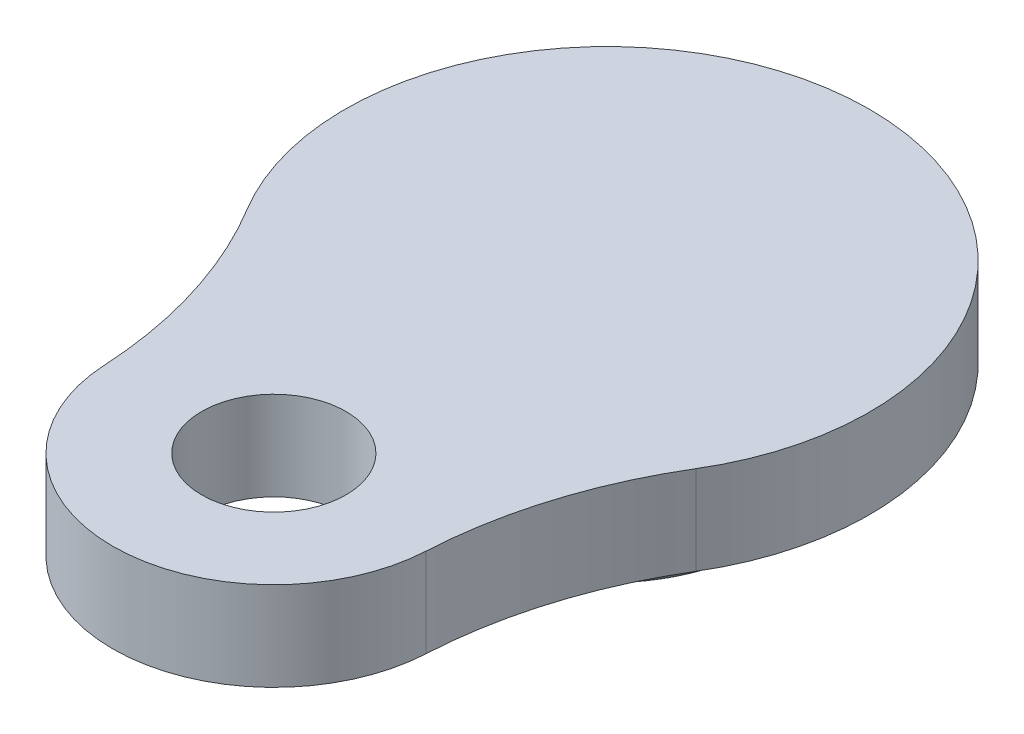
SolidWorks part; units mm, degrees
ref_plane "Front Plane" through (0, 0, 0) normal (0, 0, 1) x (1, 0, 0)
ref_plane "Top Plane" through (0, 0, 0) normal (0, 1, 0) x (1, 0, 0)
ref_plane "Right Plane" through (0, 0, 0) normal (1, 0, 0) x (0, 0, -1)
sketch "Sketch1" plane through (0, 0, 0) normal (0, 1, 0) x (1, 0, 0)
  line L0 (0, -7.5) -> (0, 0) construction
  circle A0 centre (0, 0) radius 3.9
  circle A3 centre (0, -7.5) radius 1.625
  arc A4 (-3.6198, -7.6937) -> (3.6198, -7.6937) centre (0, -7.5) ccw
  arc A5 (-5.0486, -3.0531) -> (-3.6198, -7.6937) centre (-13.6055, -8.228) cw
  arc A6 (5.0486, -3.0531) -> (-5.0486, -3.0531) centre (0, 0) ccw
  arc A7 (5.0486, -3.0531) -> (3.6198, -7.6937) centre (13.6055, -8.228) ccw
  dimension "D2" = 7.8
  dimension "D3" = 3.25
  dimension "D4" = 2
  dimension "D5" = 2
  dimension "D6" = 10
  dimension "D1" = 7.5
extrude "Boss-Extrude1" add sketch "Sketch1" along normal blind 2 contours A7 A6 A5 A4 A3 A0 | A0 region at (0, 0, 0) region at (-3.8503, 0, 5.2244)
extrude "Boss-Extrude2" add sketch "Sketch1<3>" against normal blind 2 contours A0 region at (0, 0, 0)
sketch "Sketch1<3>" plane through (0, 0, 0) normal (0, 1, 0) x (1, 0, 0) same geometry as "Sketch1"
fillet "Fillet1" radius 1 1 edges at (0, -2, 3.9)
